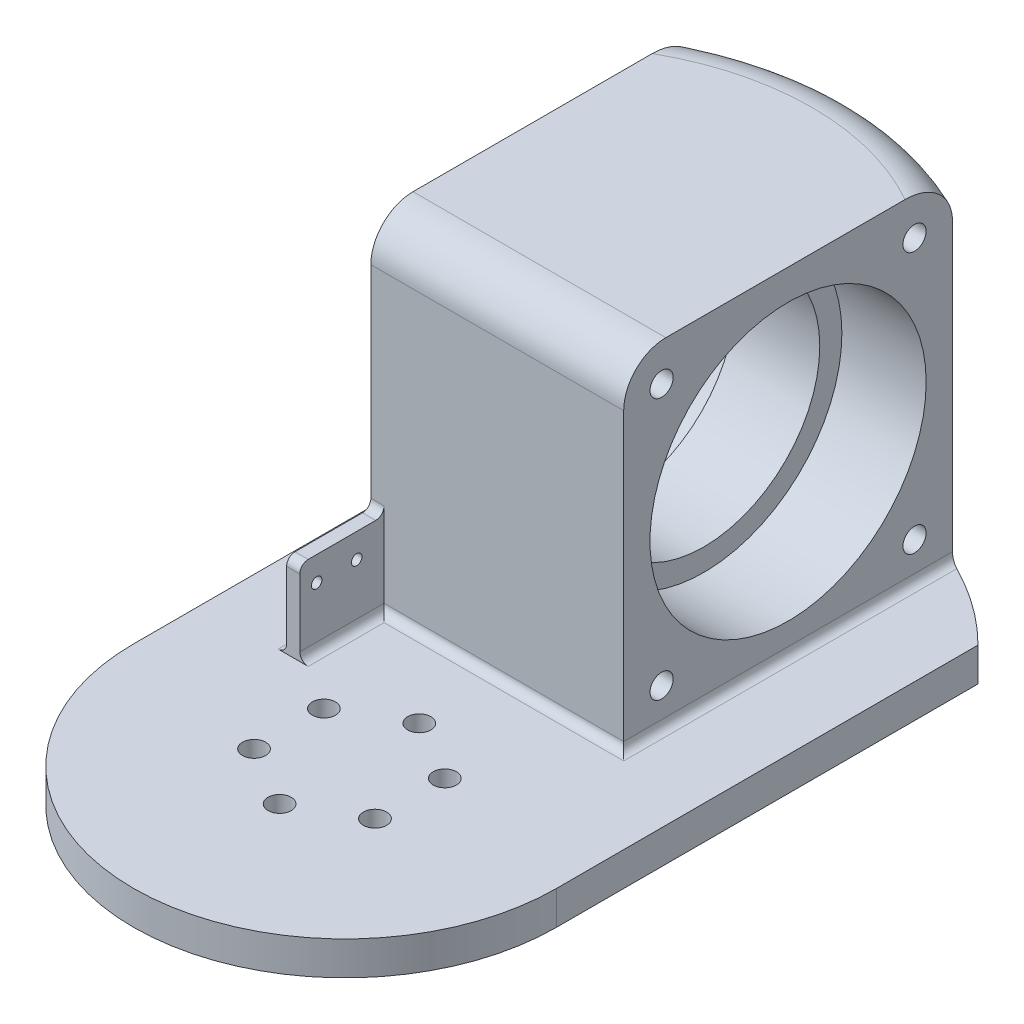
SolidWorks part; units mm, degrees
ref_plane "Front Plane" through (0, 0, 0) normal (0, 0, 1) x (1, 0, 0)
ref_plane "Top Plane" through (0, 0, 0) normal (0, 1, 0) x (1, 0, 0)
ref_plane "Right Plane" through (0, 0, 0) normal (1, 0, 0) x (0, 0, -1)
sketch "Sketch3" plane through (0, 0, 0) normal (0, 1, 0) x (1, 0, 0)
  circle A1 centre (0, 1.0493) radius 44.22
  circle A3 centre (0, 17.6193) radius 2.75
  circle A4 centre (14.35, 9.3343) radius 2.75
  circle A5 centre (14.35, -7.2357) radius 2.75
  circle A6 centre (0, -15.5207) radius 2.75
  circle A7 centre (-14.35, -7.2357) radius 2.75
  circle A8 centre (-14.35, 9.3343) radius 2.75
  dimension "D2" = 88.44
extrude "Boss-Extrude1" add sketch "Sketch3" along normal blind 1
sketch "Sketch4" plane through (0, 1, 0) normal (0, 1, 0) x (1, 0, 0)
  line L0 (-50.22, 0) -> (-50.22, 100)
  line L2 (50.22, 100) -> (50.22, 0)
  arc A1 (50.22, 0) -> (-50.22, 0) centre (0, 0) cw
  arc A2 (-50.22, 100) -> (50.22, 100) centre (0, 49.78) cw
extrude "Boss-Extrude2" add sketch "Sketch4" along normal blind 8
sketch "Sketch9" plane through (0, 0, 0) normal (0, -1, 0) x (1, 0, 0)
  circle A0 centre (0, 15.5207) radius 2.75
  circle A1 centre (14.35, 7.2357) radius 2.75
  circle A2 centre (14.35, -9.3343) radius 2.75
  circle A3 centre (0, -17.6193) radius 2.75
  circle A4 centre (-14.35, -9.3343) radius 2.75
  circle A5 centre (-14.35, 7.2357) radius 2.75
extrude "Cut-Extrude2" cut sketch "Sketch9" against normal blind 20
sketch "Sketch11" plane through (0, 9, 0) normal (0, 1, 0) x (1, 0, 0)
  line L4 (0, 36.1354) -> (-30, 36.1354)
  line L9 (-30, 36.1354) -> (-30, 114.1547)
  line L10 (0, 36.1354) -> (30, 36.1354)
  line L11 (30, 36.1354) -> (30, 114.1547)
  arc A0 (50.22, 100) -> (-50.22, 100) centre (0, 49.78) ccw construction
  arc A2 (-30, 114.1547) -> (30, 114.1547) centre (0, 49.78) cw
extrude "Boss-Extrude3" add sketch "Sketch11" along normal blind 80
sketch "Sketch12" plane through (-20, 0, 0) normal (-1, 0, 0) x (0, 0, 1)
  line L8 (-39.9083, 89) -> (-39.9083, 9)
  line L9 (-36.1354, 89) -> (-114.1547, 89)
  line L10 (-36.1354, 89) -> (-36.1354, 9)
  line L11 (-36.1354, 9) -> (-114.1547, 9)
  line L12 (-114.1547, 89) -> (-114.1547, 9)
  circle A0 centre (-75.1444, 49) radius 32.774
  dimension "D1" = 39.009
extrude "Cut-Extrude3" cut sketch "Sketch12" against normal blind 10 and the other way blind 10 contours A0
sketch "Sketch13" plane through (30, 0, 0) normal (1, 0, 0) x (0, 0, -1)
  line L1 (36.1354, 89) -> (114.1547, 89)
  line L2 (36.1354, 89) -> (36.1354, 9)
  line L3 (36.1354, 9) -> (114.1547, 9)
  line L4 (114.1547, 89) -> (114.1547, 9)
  circle A0 centre (75.145, 49) radius 32.774
  circle A1 centre (75.145, 49) radius 27.524
  dimension "D1" = 5.25
  dimension "D2" = 65.548
  dimension "D3" = 39.0096
extrude "Cut-Extrude4" cut sketch "Sketch13" against normal blind 20 contours A0
extrude "Cut-Extrude5" cut sketch "Sketch13<3>" against normal blind 66 contours A1 region at (30, 49, -75.145)
sketch "Sketch13<3>" plane through (30, 0, 0) normal (1, 0, 0) x (0, 0, -1) same geometry as "Sketch13"
sketch "Sketch14" plane through (0, 9, 0) normal (0, 1, 0) x (1, 0, 0)
  line L1 (-30, 36.1354) -> (-26.865, 36.1354)
  line L2 (-30, 36.1354) -> (-30, 16.1354)
  line L3 (-30, 16.1354) -> (-26.865, 16.1354)
  line L4 (-26.865, 36.1354) -> (-26.865, 16.1354)
extrude "Boss-Extrude4" add sketch "Sketch14" along normal blind 20
extrude "Cut-Extrude6" cut sketch "Sketch3<4>" along normal blind 1
sketch "Sketch3<4>" plane through (0, 0, 0) normal (0, 1, 0) x (1, 0, 0) same geometry as "Sketch3"
sketch "Sketch15" plane through (-30, 0, 0) normal (-1, 0, 0) x (0, 0, 1)
  line L1 (-16.1354, 29) -> (-16.1354, 9) construction
  line L2 (-33.6354, 29) -> (-33.6354, 14)
  line L3 (-114.1547, 14) -> (-16.1354, 14) construction
  circle A0 centre (-20.1354, 23.2015) radius 1.25
  circle A1 centre (-29.6354, 23.2015) radius 1.25
  dimension "D1" = 4
  dimension "D2" = 9.5
extrude "Cut-Extrude7" cut sketch "Sketch15" against normal blind 10 contours A1 | A0 region at (-30, 23.2015, -20.1354) region at (-30, 23.2015, -29.6354)
sketch "Sketch17" plane through (30, 0, 0) normal (1, 0, 0) x (0, 0, -1)
  line L0 (36.1354, 89) -> (36.1354, 9) construction
  line L1 (45.1354, 80) -> (105.1547, 80)
  line L2 (45.1354, 80) -> (45.1354, 18)
  line L3 (45.1354, 18) -> (105.1547, 18)
  line L4 (105.1547, 80) -> (105.1547, 18)
  line L5 (114.1547, 89) -> (114.1547, 9) construction
  line L6 (36.1354, 89) -> (114.1547, 89) construction
  line L8 (36.1354, 9) -> (114.1547, 9) construction
  circle A0 centre (45.1354, 80) radius 2.75
  circle A1 centre (105.1547, 80) radius 2.75
  circle A2 centre (105.1547, 18) radius 2.75
  circle A3 centre (45.1354, 18) radius 2.75
  dimension "D1" = 9
  dimension "D2" = 9
  dimension "D3" = 9
  dimension "D4" = 9
extrude "Cut-Extrude8" cut sketch "Sketch17" against normal blind 83 contours L2 A0 L1 | L1 A1 L4 | L4 A2 L3 | L3 A3 L2 | L2 A3 L3 | L3 A2 L4 | L4 A1 L1 | L1 A0 L2 region at (30, 80.389, -44.7463) region at (30, 78.8329, -46.3025) region at (30, 80.389, -105.5437) region at (30, 78.8329, -103.9875) region at (30, 19.1671, -46.3025) region at (30, 17.611, -44.7463) region at (30, 17.611, -105.5437) region at (30, 19.1671, -103.9875)
sketch "Sketch18" plane through (-30, 0, 0) normal (-1, 0, 0) x (0, 0, 1)
  circle A0 centre (-105.1547, 80) radius 6.25
  circle A1 centre (-45.1354, 80) radius 6.25
  circle A2 centre (-45.1354, 18) radius 6.25
  circle A3 centre (-105.1547, 18) radius 6.25
extrude "Cut-Extrude9" cut sketch "Sketch18" against normal blind 5.5
fillet "Fillet1" radius 10 2 edges at (0, 89, -120.8018) (0, 89, -36.1354)
fillet "Fillet2" radius 2 4 edges at (-26.865, 9, -26.1354) (1.5675, 9, -36.1354) (30, 9, -75.145) (-30, 9, -65.145)
fillet "Fillet3" radius 2 2 edges at (-28.4325, 29, -36.1354) (-28.4325, 29, -16.1354)
